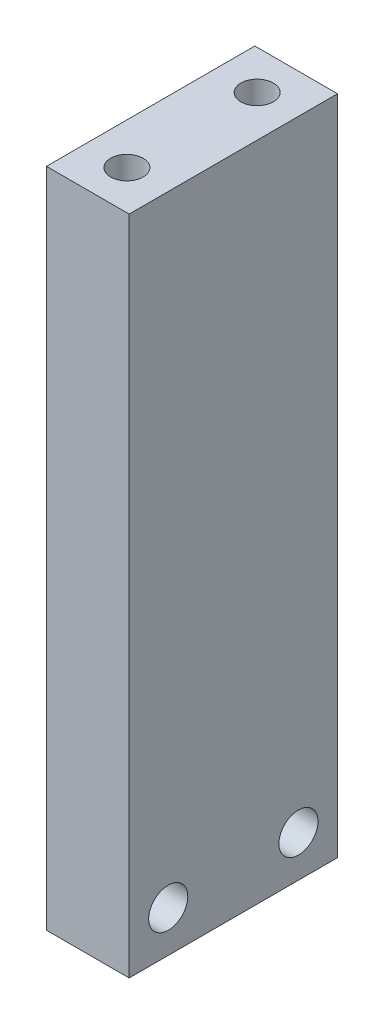
SolidWorks part; units mm, degrees
ref_plane "Front Plane" through (0, 0, 0) normal (0, 0, 1) x (1, 0, 0)
ref_plane "Top Plane" through (0, 0, 0) normal (0, 1, 0) x (1, 0, 0)
ref_plane "Right Plane" through (0, 0, 0) normal (1, 0, 0) x (0, 0, -1)
sketch "Sketch1" plane through (0, 0, 0) normal (0, 0, 1) x (1, 0, 0)
  line L1 (0, 0) -> (6.35, 0)
  line L2 (0, 0) -> (0, 50.8)
  line L3 (0, 50.8) -> (6.35, 50.8)
  line L4 (6.35, 0) -> (6.35, 50.8)
extrude "Boss-Extrude1" add sketch "Sketch1" along normal blind 16
sketch "Sketch4" plane through (6.35, 0, 0) normal (1, 0, 0) x (0, 0, -1)
  line L0 (0, 0) -> (0, 50.8) construction
  line L1 (-16, 0) -> (-16, 50.8) construction
  line L2 (-16, 0) -> (0, 0) construction
  circle A0 centre (-3, 3.175) radius 1.5
  circle A1 centre (-13, 3.175) radius 1.5
  dimension "D1" = 3
  dimension "D2" = 3
  dimension "D3" = 3
  dimension "D4" = 3
  dimension "D5" = 3.175
  dimension "D6" = 3.175
extrude "Cut-Extrude3" cut sketch "Sketch4" against normal blind 6.35
sketch "Sketch5" plane through (0, 50.8, 0) normal (0, 1, 0) x (1, 0, 0)
  line L0 (6.35, 0) -> (0, 0) construction
  line L1 (6.35, -16) -> (0, -16) construction
  line L2 (0, -16) -> (0, 0) construction
  circle A0 centre (3.175, -3) radius 1.25
  circle A1 centre (3.175, -13) radius 1.25
  dimension "D1" = 2.5
  dimension "D2" = 2.5
  dimension "D3" = 3
  dimension "D4" = 3
  dimension "D5" = 3.175
  dimension "D6" = 3.175
extrude "Cut-Extrude4" cut sketch "Sketch5" against normal blind 4
